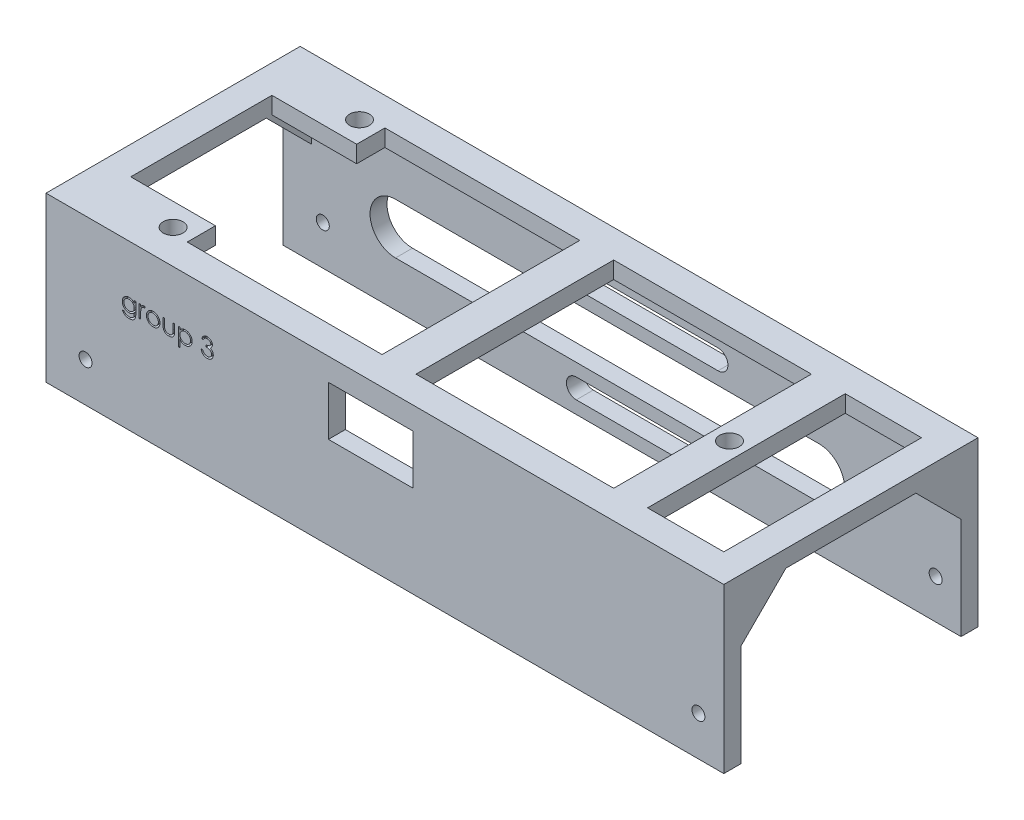
SolidWorks part; units mm, degrees
other "Markup1"
sketch "Sketch23" plane through (120, 29, 45) normal (0.0467, 0.9512, 0.3049) x (0.9885, 0, -0.1514)
sketch "Sketch24" plane through (120, 29, 45) normal (0.0467, 0.9512, 0.3049) x (0.9885, 0, -0.1514)
ref_plane "Front Plane" through (0, 0, 0) normal (0, 0, 1) x (1, 0, 0)
ref_plane "Top Plane" through (0, 0, 0) normal (0, 1, 0) x (1, 0, 0)
ref_plane "Right Plane" through (0, 0, 0) normal (1, 0, 0) x (0, 0, -1)
sketch "Sketch1" plane through (0, 0, 0) normal (0, 0, 1) x (1, 0, 0)
  line L9 (21.172, -17.9478) -> (91.172, -17.9478)
  line L10 (21.172, -17.9478) -> (21.172, -40.3878)
  line L11 (4, -8) -> (200.227, -8) construction
  line L12 (4, -8) -> (-67.5185, -8) construction
  line L13 (21.172, -40.3878) -> (91.172, -40.3878)
  line L14 (91.172, -17.9478) -> (91.172, -40.3878)
  line L15 (0, 0) -> (120, 0)
  line L16 (0, 0) -> (0, 29)
  line L17 (0, 29) -> (120, 29)
  line L18 (120, 0) -> (120, 29)
  circle A0 centre (4, 7) radius 1.15
  circle A1 centre (4, 7) radius 15 construction
  circle A3 centre (77.172, -29.1678) radius 3.6067
  circle A4 centre (116, 7) radius 15 construction
  circle A5 centre (116, 7) radius 1.15
  point P19 (21.172, -29.1678)
  dimension "D4" = 30
  dimension "D2" = 14
  dimension "D7" = 30
  dimension "D11" = 4
  dimension "D13" = 2.3
  dimension "D14" = 2.3
  dimension "D3" = 70
  dimension "D5" = 22.44
  dimension "D6" = 120
  dimension "D8" = 29
  dimension "D9" = 4
  dimension "D10" = 7
  dimension "D12" = 7
extrude "Boss-Extrude5" add sketch "Sketch1" along normal blind 45 contours L16 L15 L18 L17
shell "Shell9" thickness 3 removed face at (120, 14.5, 22.5) removed face at (60, 0, 22.5) removed face at (0, 14.5, 22.5)
sketch "Sketch3" plane through (0, 0, 0) normal (0, 0, -1) x (-1, 0, 0)
  line L0 (0, 0) -> (-120, 0) construction
  line L1 (-120, 0) -> (-120, 29) construction
  line L2 (0, 0) -> (0, 29) construction
  circle A0 centre (-7, 7) radius 1.15
  circle A1 centre (-115.5, 7) radius 1.15
  dimension "D1" = 2.3
  dimension "D2" = 2.3
  dimension "D3" = 7
  dimension "D4" = 4.5
  dimension "D5" = 7
  dimension "D6" = 7
extrude "Cut-Extrude2" cut sketch "Sketch3" against normal blind 79
sketch "Sketch6" plane through (0, 0, 0) normal (0, 0, -1) x (-1, 0, 0)
  line L0 (-76.9735, 21) -> (-51.8835, 21) construction
  line L1 (-76.9735, 22.75) -> (-51.8835, 22.75)
  line L2 (-76.9735, 19.25) -> (-51.8835, 19.25)
  line L7 (41.5249, -18.7743) -> (41.5249, -41.2143) construction
  line L8 (-94.8735, 12.5) -> (-19.8735, 12.5) construction
  line L9 (-94.8735, 17) -> (-19.8735, 17)
  line L10 (-94.8735, 8) -> (-19.8735, 8)
  line L11 (-19.8735, 12.5) -> (-17.326, 12.5) construction
  line L12 (-76.9735, 4) -> (-51.8835, 4) construction
  line L13 (-76.9735, 2.25) -> (-51.8835, 2.25)
  line L14 (-76.9735, 5.75) -> (-51.8835, 5.75)
  line L15 (4.7849, -29.9943) -> (74.7849, -29.9943) construction
  line L20 (4.7849, -18.7743) -> (74.7849, -18.7743)
  line L21 (4.7849, -18.7743) -> (4.7849, -41.2143)
  line L22 (4.7849, -41.2143) -> (74.7849, -41.2143)
  line L23 (74.7849, -18.7743) -> (74.7849, -41.2143)
  line L24 (-120, 0) -> (-120, 29) construction
  line L25 (63.3749, -18.7743) -> (63.3749, -41.2143) construction
  line L26 (0, 29) -> (-120, 29) construction
  arc A4 (-94.8735, 17) -> (-94.8735, 8) centre (-94.8735, 12.5) ccw
  arc A5 (-76.9735, 22.75) -> (-76.9735, 19.25) centre (-76.9735, 21) ccw
  arc A6 (-51.8835, 19.25) -> (-51.8835, 22.75) centre (-51.8835, 21) ccw
  arc A7 (-19.8735, 8) -> (-19.8735, 17) centre (-19.8735, 12.5) ccw
  arc A8 (-76.9735, 2.25) -> (-76.9735, 5.75) centre (-76.9735, 4) cw
  arc A9 (-51.8835, 5.75) -> (-51.8835, 2.25) centre (-51.8835, 4) cw
  circle A15 centre (16.1349, -29.9943) radius 1.5
  circle A16 centre (36.3249, -21.4943) radius 1.5
  circle A17 centre (36.3249, -38.4943) radius 1.5
  circle A18 centre (36.3249, -38.4943) radius 1.5
  circle A19 centre (27.0349, -29.9943) radius 2.3201
  point P11 (-64.4285, 21)
  point P19 (-57.3735, 12.5)
  point P31 (-64.4285, 4)
  dimension "D8" = 1.75
  dimension "D13" = 4.5
  dimension "D10" = 3
  dimension "D14" = 3
  dimension "D9" = 25.09
  dimension "D2" = 8.5
  dimension "D3" = 17.9
  dimension "D4" = 70
  dimension "D5" = 22.44
  dimension "D6" = 36.74
  dimension "D7" = 11.35
  dimension "D11" = 5.2
  dimension "D12" = 8.5
  dimension "D15" = 22.25
  dimension "D16" = 75
  dimension "D17" = 25.1265
  dimension "D18" = 11.41
  dimension "D19" = 16.5
extrude "Cut-Extrude8" cut sketch "Sketch6" against normal blind 23 contours L10 A7 L9 | L2 A6 L1 A5 | L13 A9 L14 A8 region at (64.4285, 21, 0) region at (57.3735, 12.5, 0)
sketch "Sketch7" plane through (0, 0, 45) normal (0, 0, 1) x (1, 0, 0)
  line L1 (50, 25) -> (65, 25)
  line L2 (50, 25) -> (50, 16.25)
  line L3 (50, 16.25) -> (65, 16.25)
  line L4 (65, 25) -> (65, 16.25)
  line L5 (0, 0) -> (120, 0) construction
  line L7 (0, 0) -> (0, 29) construction
  dimension "D1" = 50
  dimension "D2" = 15
  dimension "D3" = 8.75
  dimension "D4" = 25
extrude "Cut-Extrude9" cut sketch "Sketch7" against normal blind 20
sketch "Sketch13" plane through (0, 29, 0) normal (0, 1, 0) x (1, 0, 0)
  line L1 (0, 0) -> (120, 0) construction
  line L4 (5, -5) -> (115, -5)
  line L5 (5, -5) -> (5, -40)
  line L6 (5, -40) -> (115, -40)
  line L8 (0, -45) -> (0, 0) construction
  line L16 (115, -5) -> (115, -40)
  line L17 (120, -45) -> (120, 0) construction
  dimension "D1" = 5
  dimension "D2" = 5
  dimension "D5" = 5
  dimension "D6" = 35
extrude "Cut-Extrude14" cut sketch "Sketch13" against normal blind 10
sketch "Sketch17" plane through (0, 29, 0) normal (0, 1, 0) x (1, 0, 0)
  line L0 (0, -22.5) -> (120, -22.5) construction
  line L1 (5, -5) -> (20, -5)
  line L2 (5, -5) -> (5, -10)
  line L3 (5, -10) -> (20, -10)
  line L4 (20, -5) -> (20, -10)
  line L5 (5, -40) -> (20, -40)
  line L6 (5, -40) -> (5, -35)
  line L7 (5, -35) -> (20, -35)
  line L8 (20, -40) -> (20, -35)
  line L17 (0, -45) -> (0, 0) construction
  line L18 (120, -45) -> (120, 0) construction
  line L25 (115, -5) -> (5, -5) construction
  line L26 (95.5, -5) -> (101.5, -5)
  line L27 (95.5, -5) -> (95.5, -40)
  line L28 (95.5, -40) -> (101.5, -40)
  line L29 (101.5, -5) -> (101.5, -40)
  line L30 (5, -40) -> (115, -40) construction
  line L32 (54.5, -5) -> (60.5, -5)
  line L33 (54.5, -5) -> (54.5, -40)
  line L34 (54.5, -40) -> (60.5, -40)
  line L35 (60.5, -5) -> (60.5, -40)
  circle A0 centre (16.5, -39) radius 1.75
  circle A1 centre (16.5, -6) radius 1.75
  circle A2 centre (98.5, -22.5) radius 1.75
  point P41 (98.5, -5)
  line M10 (5, -40) -> (5, -5)
  line M11 (5, -5) -> (115, -5)
  line M13 (115, -40) -> (5, -40)
  dimension "D3" = 3.5
  dimension "D6" = 3.5
  dimension "D11" = 33
  dimension "D12" = 16.5
  dimension "D13" = 3.5
  dimension "D1" = 5
  dimension "D2" = 15
  dimension "D4" = 5
  dimension "D5" = 15
  dimension "D7" = 6
  dimension "D8" = 18.5
  dimension "D9" = 6
  dimension "D10" = 35
extrude "Boss-Extrude6" add sketch "Sketch17" against normal blind 3 contours A1 L3 L4 M11 M10 | L1 A1 | A0 L8 L7 M13 M10 | L5 A0 | L33 L32 L35 L34 | L27 L26 L29 L28 region at (12.0151, 29, 7.6523) region at (16.5, 29, 6.2435) region at (12.0151, 29, 37.3477) region at (16.5, 29, 38.7565)
extrude "Cut-Extrude16" cut sketch "Sketch17<4>" against normal blind 10 contours A2 L0 | L0 A2 | L1 A1 | L1 A1 | L5 A0 | L5 A0 | A2 region at (98.5, 29, 21.7573) region at (98.5, 29, 23.2427) region at (16.5, 29, 4.6937) region at (16.5, 29, 6.2435) region at (16.5, 29, 38.7565) region at (16.5, 29, 40.3063)
sketch "Sketch17<4>" plane through (0, 29, 0) normal (0, 1, 0) x (1, 0, 0) same geometry as "Sketch17"
sketch "Sketch20" plane through (0, 0, 45) normal (0, 0, 1) x (1, 0, 0)
  line L0 (13.2558, 18.0126) -> (38.9246, 18.0126) construction
  text T0 "group 3"
extrude "Cut-Extrude15" cut sketch "Sketch20" against normal blind 1.5
sketch "Sketch21" plane through (0, 0, 0) normal (-1, 0, 0) x (0, 0, 1)
  line L0 (3, 26) -> (3, 18)
  line L1 (3, 0) -> (3, 26) construction
  line L2 (3, 18) -> (11, 26)
  line L3 (42, 26) -> (3, 26) construction
  line L4 (11, 26) -> (3, 26)
  line L5 (42, 26) -> (34, 26)
  line L6 (34, 26) -> (42, 18)
  line L7 (42, 0) -> (42, 26) construction
  line L8 (42, 18) -> (42, 26)
  dimension "D1" = 8
  dimension "D2" = 8
  dimension "D3" = 8
  dimension "D4" = 8
extrude "Boss-Extrude7" add sketch "Sketch21" against normal blind 5
sketch "Sketch22" plane through (120, 0, 0) normal (1, 0, 0) x (0, 0, -1)
  line L0 (-42, 26) -> (-42, 18)
  line L1 (-42, 18) -> (-34, 26)
  line L2 (-34, 26) -> (-42, 26)
  line L3 (-11, 26) -> (-3, 26)
  line L4 (-3, 26) -> (-3, 18)
  line L5 (-3, 18) -> (-11, 26)
extrude "Boss-Extrude8" add sketch "Sketch22" against normal blind 5
equation "\"slot­_width\"=25.09"
equation "\"D9@Sketch6\"=\"slot­_width\""
